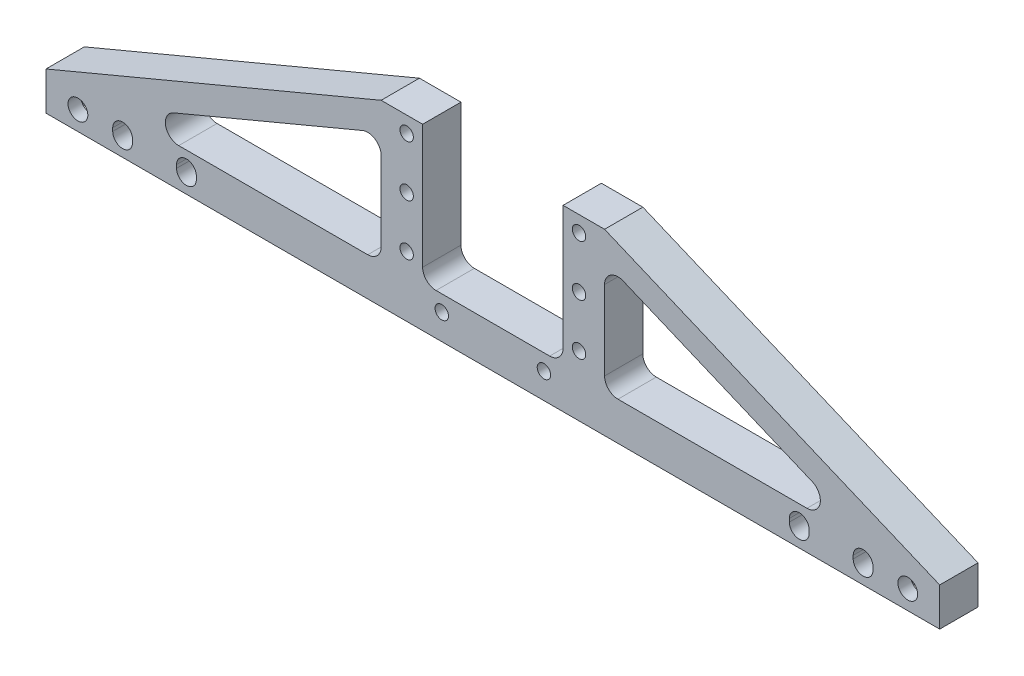
SolidWorks part; units mm, degrees
ref_plane "正面" through (0, 0, 0) normal (0, 0, 1) x (1, 0, 0)
ref_plane "平面" through (0, 0, 0) normal (0, 1, 0) x (1, 0, 0)
ref_plane "右側面" through (0, 0, 0) normal (1, 0, 0) x (0, 0, -1)
sketch "ｽｹｯﾁ1" plane through (0, 0, 0) normal (0, 0, 1) x (1, 0, 0)
  line L0 (-13.5, 21.5) -> (-13.5, 13.5) construction
  line L5 (-13.5, 13.5) -> (-13.5, 5.5) construction
  line L6 (-13.5, 5.5) -> (-13.5, 0) construction
  line L7 (-13.5, 0) -> (-8, 0) construction
  line L8 (-8, 0) -> (8, 0) construction
  line L9 (8, 0) -> (13.5, 0) construction
  line L10 (13.5, 0) -> (13.5, 5.5) construction
  line L11 (13.5, 5.5) -> (13.5, 13.5) construction
  line L12 (13.5, 13.5) -> (13.5, 21.5) construction
  line L13 (-11, 4.6) -> (-11, 24)
  line L14 (-11, 24) -> (-17.5, 24)
  line L15 (-17.5, 24) -> (-17.5, -4) construction
  line L16 (-17.5, -4) -> (17.5, -4)
  line L17 (17.5, -4) -> (17.5, 24) construction
  line L18 (17.5, 24) -> (11, 24)
  line L19 (11, 24) -> (11, 4.6)
  line L20 (8.9, 2.5) -> (-8.9, 2.5)
  line L21 (-17.5, 24) -> (-70, 2)
  line L22 (-70, -4) -> (-17.5, -4)
  line L23 (-17.5, 4.1) -> (-17.5, 16.5061)
  line L24 (-20.4116, 18.4429) -> (-50.017, 6.0368)
  line L25 (-49.2054, 2) -> (-19.6, 2)
  line L26 (-70, 2) -> (-70, -4)
  line L27 (-70, -1) -> (-65, -1) construction
  line L28 (-65, -1) -> (-65, -4) construction
  line L29 (0, -4) -> (0, 24) construction
  line L30 (70, -4) -> (17.5, -4)
  line L31 (70, 2) -> (70, -4)
  line L32 (17.5, 24) -> (70, 2)
  line L33 (20.4116, 18.4429) -> (50.017, 6.0368)
  line L34 (17.5, 4.1) -> (17.5, 16.5061)
  line L35 (49.2054, 2) -> (19.6, 2)
  circle A0 centre (-13.5, 5.5) radius 1.05
  circle A1 centre (-8, 0) radius 1.05
  circle A2 centre (8, 0) radius 1.05
  circle A3 centre (-13.5, 13.5) radius 1.05
  circle A4 centre (-13.5, 21.5) radius 1.05
  circle A5 centre (13.5, 21.5) radius 1.05
  circle A6 centre (13.5, 13.5) radius 1.05
  circle A7 centre (13.5, 5.5) radius 1.05
  arc A8 (-17.5, 4.1) -> (-19.6, 2) centre (-19.6, 4.1) cw
  arc A9 (-50.017, 6.0368) -> (-49.2054, 2) centre (-49.2054, 4.1) ccw
  arc A10 (-17.5, 16.5061) -> (-20.4116, 18.4429) centre (-19.6, 16.5061) ccw
  circle A11 centre (-65, -1) radius 1.55
  circle A12 centre (65, -1) radius 1.55
  arc A13 (17.5, 16.5061) -> (20.4116, 18.4429) centre (19.6, 16.5061) cw
  arc A14 (17.5, 4.1) -> (19.6, 2) centre (19.6, 4.1) ccw
  arc A15 (50.017, 6.0368) -> (49.2054, 2) centre (49.2054, 4.1) cw
  arc A16 (11, 4.6) -> (8.9, 2.5) centre (8.9, 4.6) cw
  arc A17 (-11, 4.6) -> (-8.9, 2.5) centre (-8.9, 4.6) ccw
  point P0 (0, 0)
  point P1 (0, 0)
  point P35 (-17.5, 2)
  point P40 (-17.5, 19.663)
  dimension "D3" = 2.1
  dimension "D15" = 2.1
  dimension "D17" = 3.1
  dimension "D19" = 2.1
  dimension "D1" = 5.5
  dimension "D2" = 8
  dimension "D4" = 27
  dimension "D5" = 2.5
  dimension "D6" = 2.5
  dimension "D7" = 2.5
  dimension "D8" = 4
  dimension "D9" = 4
  dimension "D10" = 2.5
  dimension "D11" = 4
  dimension "D12" = 70
  dimension "D13" = 4
  dimension "D14" = 6
  dimension "D16" = 6
  dimension "D18" = 5
extrude "ﾎﾞｽ - 押し出し1" add sketch "ｽｹｯﾁ1" along normal blind 6
sketch "ｽｹｯﾁ2" plane through (0, 0, 6) normal (0, 0, 1) x (1, 0, 0)
  line L0 (-70, -1) -> (-48, -1) construction
  line L1 (-70, 2) -> (-70, -4) construction
  line L2 (0, -4) -> (0, 2.5) construction
  line L3 (-70, -4) -> (70, -4) construction
  line L4 (8.9, 2.5) -> (-8.9, 2.5) construction
  circle A0 centre (-48, -1) radius 1.55
  circle A1 centre (48, -1) radius 1.55
  circle A2 centre (-58, -1) radius 1.55
  circle A3 centre (58, -1) radius 1.55
  dimension "D1" = 3.1
  dimension "D2" = 22
  dimension "D3" = 10
extrude "ｶｯﾄ - 押し出し1" cut sketch "ｽｹｯﾁ2" against normal blind 3
sketch "ｽｹｯﾁ3" plane through (0, 0, 0) normal (0, 0, -1) x (-1, 0, 0)
  line L0 (-58, -0.75) -> (-58, -1.25) construction
  line L1 (-56.45, -0.75) -> (-56.45, -1.25)
  line L2 (-59.55, -0.75) -> (-59.55, -1.25)
  line L3 (-48, -0.75) -> (-48, -1.25) construction
  line L4 (-46.45, -0.75) -> (-46.45, -1.25)
  line L5 (-49.55, -0.75) -> (-49.55, -1.25)
  line L6 (0, 2.5) -> (0, -4) construction
  line L7 (-8.9, 2.5) -> (8.9, 2.5) construction
  line L8 (70, -4) -> (-70, -4) construction
  line L9 (58, -0.75) -> (58, -1.25) construction
  line L10 (56.45, -0.75) -> (56.45, -1.25)
  line L11 (59.55, -0.75) -> (59.55, -1.25)
  line L12 (48, -0.75) -> (48, -1.25) construction
  line L13 (46.45, -0.75) -> (46.45, -1.25)
  line L14 (49.55, -0.75) -> (49.55, -1.25)
  arc A0 (-56.45, -0.75) -> (-59.55, -0.75) centre (-58, -0.75) ccw
  arc A1 (-59.55, -1.25) -> (-56.45, -1.25) centre (-58, -1.25) ccw
  circle A2 centre (-58, -1) radius 1.55 construction
  arc A3 (-46.45, -0.75) -> (-49.55, -0.75) centre (-48, -0.75) ccw
  arc A4 (-49.55, -1.25) -> (-46.45, -1.25) centre (-48, -1.25) ccw
  arc A5 (56.45, -0.75) -> (59.55, -0.75) centre (58, -0.75) cw
  arc A6 (59.55, -1.25) -> (56.45, -1.25) centre (58, -1.25) cw
  arc A7 (46.45, -0.75) -> (49.55, -0.75) centre (48, -0.75) cw
  arc A8 (49.55, -1.25) -> (46.45, -1.25) centre (48, -1.25) cw
  point P2 (-58, -1)
  point P13 (-48, -1)
  point P25 (58, -1)
  point P32 (48, -1)
  dimension "D1" = 0.5
  dimension "D2" = 2
extrude "ｶｯﾄ - 押し出し2" cut sketch "ｽｹｯﾁ3" against normal through all
sketch "ｽｹｯﾁ4" plane through (0, 0, 0) normal (0, 0, -1) x (-1, 0, 0)
  line L0 (-68, -1) -> (-68, -4)
  line L1 (70, -4) -> (-70, -4) construction
  line L2 (-68, -4) -> (-62, -4)
  line L3 (-62, -4) -> (-62, -1)
  line L4 (0, -4) -> (0, 2.5) construction
  line L5 (-8.9, 2.5) -> (8.9, 2.5) construction
  line L6 (62, -4) -> (62, -1)
  line L7 (68, -4) -> (62, -4)
  line L8 (68, -1) -> (68, -4)
  arc A0 (-62, -1) -> (-68, -1) centre (-65, -1) ccw
  arc A1 (62, -1) -> (68, -1) centre (65, -1) cw
  dimension "D1" = 6
extrude "ｶｯﾄ - 押し出し3" cut sketch "ｽｹｯﾁ4" against normal blind 4
sketch "ｽｹｯﾁ6" plane through (0, 0, 0) normal (0, 0, -1) x (-1, 0, 0)
  line L0 (0, -4) -> (0, 24.1954) construction
  line L1 (62, -4) -> (-62, -4) construction
  circle A0 centre (-13.5, 21.5) radius 1.9
  circle A1 centre (-13.5, 13.5) radius 1.9
  circle A2 centre (-13.5, 5.5) radius 1.9
  circle A3 centre (-8, 0) radius 1.9
  circle A4 centre (8, 0) radius 1.9
  circle A5 centre (13.5, 5.5) radius 1.9
  circle A6 centre (13.5, 13.5) radius 1.9
  circle A7 centre (13.5, 21.5) radius 1.9
  dimension "D1" = 3.8
  dimension "D2" = 3
extrude "ｶｯﾄ - 押し出し4" cut sketch "ｽｹｯﾁ6" against normal blind 3
